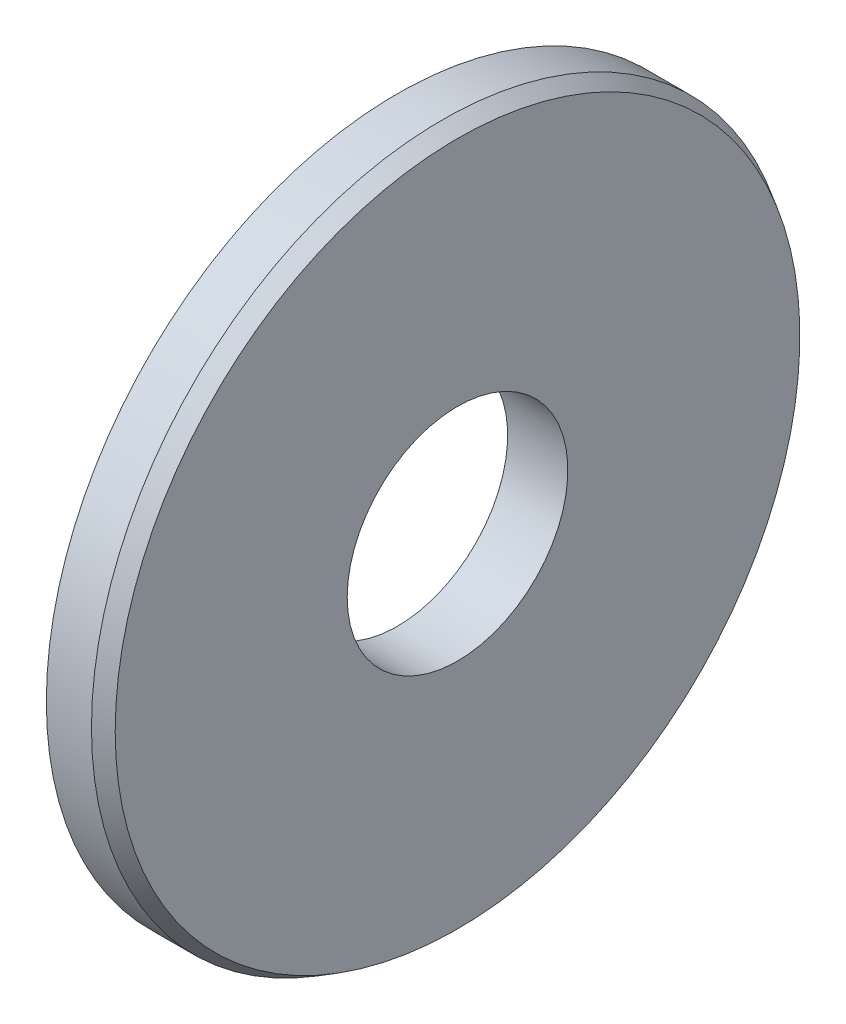
SolidWorks part; units mm, degrees
ref_plane "Спереди" through (0, 0, 0) normal (0, 0, 1) x (1, 0, 0)
ref_plane "Сверху" through (0, 0, 0) normal (0, 1, 0) x (1, 0, 0)
ref_plane "Справа" through (0, 0, 0) normal (1, 0, 0) x (0, 0, -1)
sketch "Эскиз1" plane through (0, 0, 0) normal (0, 0, 1) x (1, 0, 0)
  line L0 (-1000, 0) -> (49000, 0) construction
  line L1 (0, 0.5) -> (0, -0.5) construction
  line L2 (-0.15, 0.55) -> (0.15, 0.55)
  line L3 (-0.15, 0.55) -> (-0.15, 1.75)
  line L4 (-0.15, 1.75) -> (0.15, 1.75)
  line L5 (0.15, 0.55) -> (0.15, 1.75)
  point P7 (0, 0.55)
  point P11 (0, 0)
revolve "Повернуть1" add sketch "Эскиз1" angle 360 about L0
chamfer "Фаска1" distance 0.075 angle 30 1 edges at (0.15, 0, 1.75) first distance on face at (-0.15, 0, 1.75)
equation "\"а\"= \"S_@Эскиз1\" * 0.25"
equation "\"D1@Фаска1\"=\"а\""
